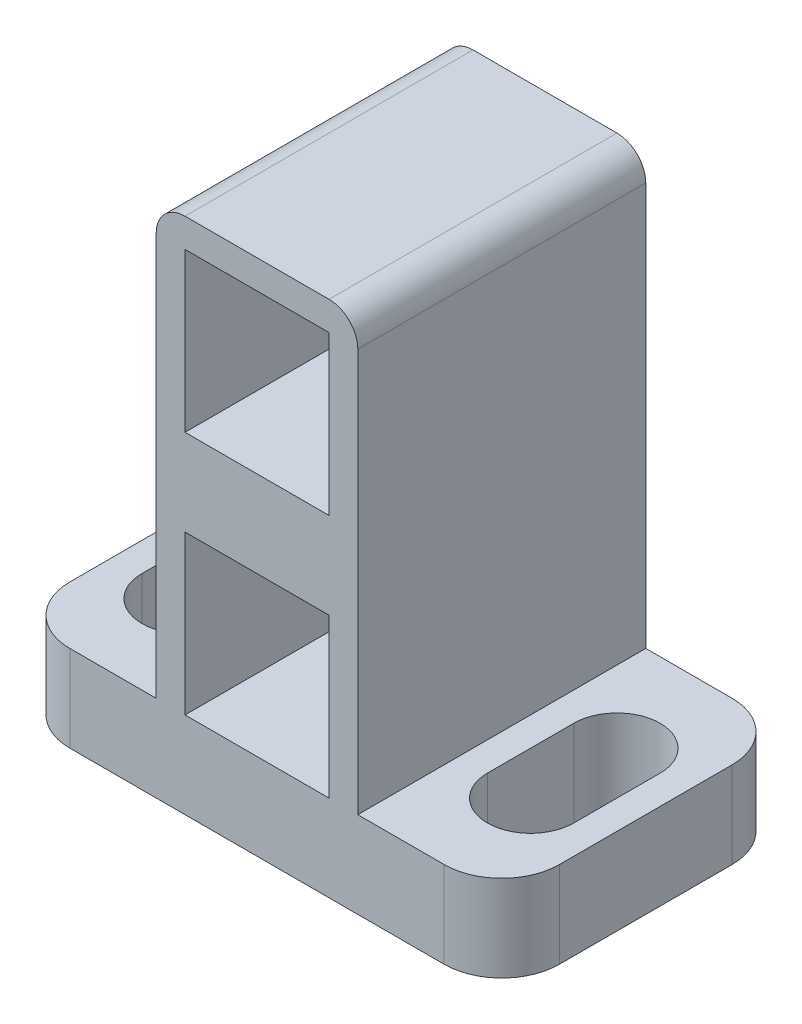
SolidWorks part; units mm, degrees
ref_plane "Front Plane" through (0, 0, 0) normal (0, 0, 1) x (1, 0, 0)
ref_plane "Top Plane" through (0, 0, 0) normal (0, 1, 0) x (1, 0, 0)
ref_plane "Right Plane" through (0, 0, 0) normal (1, 0, 0) x (0, 0, -1)
sketch "Sketch1" plane through (0, 0, 0) normal (0, 0, 1) x (1, 0, 0)
  line L1 (-3.5, -9) -> (3.5, -9)
  line L2 (-3.5, -9) -> (-3.5, 9)
  line L3 (-3.5, 9) -> (3.5, 9)
  line L4 (3.5, -9) -> (3.5, 9)
  line L5 (-3.5, -9) -> (3.5, 9) construction
  line L6 (-3.5, 9) -> (3.5, -9) construction
  point P0 (0, 0)
  dimension "D1" = 7
  dimension "D2" = 18
extrude "Boss-Extrude1" add sketch "Sketch1" along normal blind 8
sketch "Sketch3" plane through (0, 0, 0) normal (0, 0, -1) x (-1, 0, 0)
  line L1 (3.5, 9) -> (-3.5, 9)
  line L2 (3.5, 9) -> (3.5, -9)
  line L3 (3.5, -9) -> (-3.5, -9)
  line L4 (-3.5, 9) -> (-3.5, -9)
extrude "Boss-Extrude2" add sketch "Sketch3" along normal blind 2
ref_plane "Plane1" through (0, 1, 0) normal (0, 1, 0) x (1, 0, 0)
sketch "Sketch2" plane through (0, 0, 8) normal (0, 0, 1) x (1, 0, 0)
  line L1 (-2.5, 2.5) -> (2.5, 2.5)
  line L2 (-2.5, 2.5) -> (-2.5, 8)
  line L3 (-2.5, 8) -> (2.5, 8)
  line L4 (2.5, 2.5) -> (2.5, 8)
  line L5 (-2.5, 2.5) -> (2.5, 8) construction
  line L6 (-2.5, 8) -> (2.5, 2.5) construction
  line L13 (-3.5, 9) -> (-2.5, 9) construction
  line L14 (-3.5, 9) -> (-3.5, 8) construction
  line L15 (-3.5, 8) -> (-2.5, 8) construction
  line L16 (-2.5, 9) -> (-2.5, 8) construction
  line L19 (0, 9) -> (0, -9) construction
  line L20 (3.5, 9) -> (-3.5, 9) construction
  line L21 (-3.5, -9) -> (3.5, -9) construction
  point P0 (0, 5.25)
  dimension "D1" = 5.5
  dimension "D2" = 1
extrude "Cut-Extrude1" cut sketch "Sketch2" against normal offset from surface (8 mm away) 2 up to face at (0, 0, -2)
sketch "Sketch4" plane through (0, 0, 0) normal (0, 0, 1) x (1, 0, 0)
  line L0 (2.5, 8) -> (-2.5, 8) construction
  line L1 (-2.5, 2.5) -> (2.5, 2.5) construction
  line L2 (-2.5, 2.5) -> (-2.5, 8) construction
  line L3 (-2.5, 8) -> (2.5, 8) construction
  line L4 (2.5, 2.5) -> (2.5, 8) construction
  line L5 (-2.5, 2.5) -> (2.5, 8) construction
  line L6 (-2.5, 8) -> (2.5, 2.5) construction
  line L7 (2.5, 2.5) -> (2.5, 8) construction
  line L9 (-2.5, 8) -> (-2.5, 2.5) construction
  line L10 (-2.5, 2.5) -> (2.5, 2.5) construction
  circle A0 centre (0, 5.25) radius 1
  dimension "D1" = 2
extrude "Cut-Extrude2" cut sketch "Sketch4" against normal through all
mirror "Mirror1" about plane through (0, 1, 0) normal (0, 1, 0) of "Cut-Extrude2", "Cut-Extrude1"
sketch "Sketch5" plane through (0, -9, 0) normal (0, -1, 0) x (1, 0, 0)
  line L0 (3.5, -2) -> (-3.5, -2) construction
  line L1 (3.5, 8) -> (8.5, 8)
  line L2 (3.5, 8) -> (3.5, -2)
  line L3 (3.5, -2) -> (8.5, -2)
  line L4 (8.5, 8) -> (8.5, -2)
  line L5 (6, 4.5) -> (6, 1.5) construction
  line L6 (7.5, 4.5) -> (7.5, 1.5)
  line L7 (4.5, 4.5) -> (4.5, 1.5)
  line L8 (3.5, 3) -> (8.5, 3) construction
  line L11 (6, -2) -> (6, 8) construction
  arc A0 (7.5, 4.5) -> (4.5, 4.5) centre (6, 4.5) ccw
  arc A1 (4.5, 1.5) -> (7.5, 1.5) centre (6, 1.5) ccw
  point P9 (6, 3)
  dimension "D1" = 5
  dimension "D2" = 3
  dimension "D3" = 3
extrude "Boss-Extrude3" add sketch "Sketch5" against normal blind 3
fillet "Fillet1" radius 2 2 edges at (8.5, -7.5, -2) (8.5, -7.5, 8)
mirror "Mirror2" about plane through (0, 0, 0) normal (1, 0, 0) of "Fillet1", "Boss-Extrude3"
fillet "Fillet2" radius 1 2 edges at (3.5, 9, 3) (-3.5, 9, 3)
